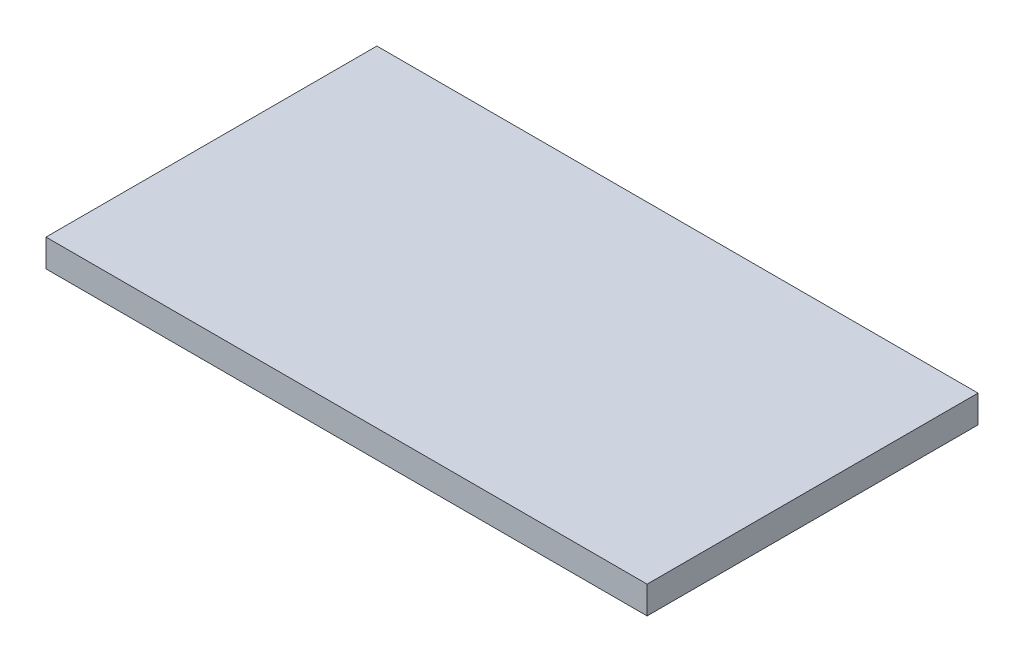
SolidWorks part; units mm, degrees
ref_plane "Front" through (0, 0, 0) normal (0, 0, 1) x (1, 0, 0)
ref_plane "Top" through (0, 0, 0) normal (0, 1, 0) x (1, 0, 0)
ref_plane "Right" through (0, 0, 0) normal (1, 0, 0) x (0, 0, -1)
sketch "Sketch1" plane through (0, 0, 0) normal (0, 1, 0) x (1, 0, 0)
  line L1 (-54.5, -30) -> (54.5, -30)
  line L2 (-54.5, -30) -> (-54.5, 30)
  line L3 (-54.5, 30) -> (54.5, 30)
  line L4 (54.5, -30) -> (54.5, 30)
  line L5 (-54.5, -30) -> (54.5, 30) construction
  line L6 (-54.5, 30) -> (54.5, -30) construction
  line L67 (-54.5, -30) -> (54.5, -30)
  point P0 (0, 0)
  point P6 (0, 0)
  point P7 (-55.4858, -30)
  point P8 (-54.4287, -30)
  point P9 (0, 0)
  point P10 (0, 0)
  point P11 (0, 0)
  point P12 (0, 0)
  point P13 (56.705, -30)
  point P14 (0, 0)
  point P15 (0, 0)
  point P16 (0, 0)
  point P17 (0, 0)
  point P18 (0, 0)
  point P19 (0, 0)
  point P20 (0, 0)
  point P22 (0, 0)
  dimension "D1" = 109
  dimension "D2" = 60
extrude "Boss-Extrude1" add sketch "Sketch1" along normal blind 5 contours L1 L4 L3 L2 region at (0, 0, 0)
